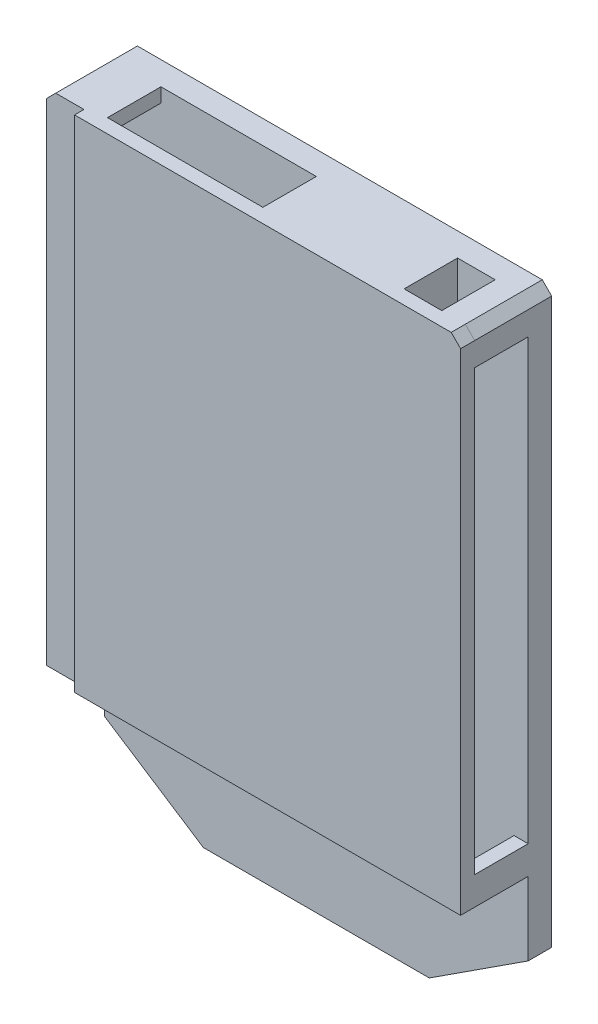
SolidWorks part; units mm, degrees
ref_plane "Front Plane" through (0, 0, 0) normal (0, 0, 1) x (1, 0, 0)
ref_plane "Top Plane" through (0, 0, 0) normal (0, 1, 0) x (1, 0, 0)
ref_plane "Right Plane" through (0, 0, 0) normal (1, 0, 0) x (0, 0, -1)
sketch "Sketch2" plane through (0, 0, 0) normal (0, 0, 1) x (1, 0, 0)
  line L0 (-45, 122) -> (-45, 0.1976)
  line L1 (-24, -13.44) -> (24, -13.44)
  line L2 (45, 0.1976) -> (45, 122)
  line L3 (45, 122) -> (-45, 122)
  line L4 (-45, 0.1976) -> (-24, -13.44)
  line L5 (24, -13.44) -> (45, 0.1976)
  line L6 (49.2788, -47.9725) -> (58.518, -41.9725) construction
  line L7 (-61.482, -41.9725) -> (-52.2428, -47.9725) construction
  point P15 (-45, 6.7015)
  point P16 (0, 0)
  point P17 (-45, 0)
  dimension "D1" = 48
  dimension "D2" = 135.44
extrude "Boss-Extrude1" add sketch "Sketch2" along normal blind 5
chamfer "Chamfer1" distance 2 2 edges at (-45, 122, 2.5) (45, 122, 2.5)
sketch "Sketch4" plane through (0, 0, 5) normal (0, 0, 1) x (1, 0, 0)
  line L0 (-45, 120) -> (-43, 122)
  line L1 (-43, 122) -> (-33, 122)
  line L2 (43, 122) -> (-43, 122) construction
  line L3 (-33, 122) -> (-33, 119)
  line L4 (-33, 119) -> (-41.7574, 119)
  line L5 (-41.7574, 119) -> (-42, 118.7574)
  line L9 (-45, 118.7574) -> (-45, 120)
  line L10 (-42, 118.7574) -> (-45, 118.7574)
  line L11 (-45, 15.7574) -> (-33, 15.7574)
  line L12 (-45, 120) -> (-45, 0.1976) construction
  line L13 (-33, 15.7574) -> (-33, 18.7574)
  line L14 (-33, 18.7574) -> (-45, 18.7574)
  line L15 (-45, 18.7574) -> (-45, 15.7574)
  line L16 (0, 122) -> (30, 122)
  line L17 (30, 122) -> (30, 108)
  line L18 (30, 108) -> (27, 108)
  line L19 (27, 108) -> (27, 119)
  line L20 (27, 119) -> (0, 119)
  line L21 (0, 119) -> (0, 122)
  line L22 (0, 15.7574) -> (30, 15.7574)
  line L23 (30, 15.7574) -> (30, 29.7574)
  line L24 (30, 29.7574) -> (27, 29.7574)
  line L25 (27, 29.7574) -> (27, 18.7574)
  line L26 (27, 18.7574) -> (0, 18.7574)
  line L27 (0, 18.7574) -> (0, 15.7574)
  point P25 (-45, 116.6472)
  point P30 (-39.5053, 120.0532)
  point P31 (-40.4031, 120.3543)
  point P32 (-8.4136, 119)
  point P33 (0, 0)
  dimension "D1" = 100
  dimension "D2" = 3
  dimension "D3" = 3
  dimension "D4" = 3
  dimension "D5" = 3
  dimension "D6" = 3
  dimension "D7" = 3
  dimension "D8" = 72
  dimension "D9" = 14
  dimension "D10" = 30
  dimension "D11" = 12
extrude "Boss-Extrude2" add sketch "Sketch4" along normal blind 11.35
sketch "Sketch5" plane through (0, 0, 16.35) normal (0, 0, 1) x (1, 0, 0)
  line L0 (-33, 122) -> (-43, 122) construction
  line L1 (45, 15.7574) -> (-45, 15.7574)
  line L2 (45, 15.7574) -> (45, 122)
  line L3 (45, 122) -> (-43, 122)
  line L4 (-45, 15.7574) -> (-45, 120)
  line L6 (-45, 118.7574) -> (-45, 18.7574) construction
  line L7 (-43, 122) -> (-45, 120)
  line L8 (45, 0.1976) -> (45, 120) construction
  line L9 (0, 15.7574) -> (30, 15.7574) construction
  point P1 (-45, 122)
  point P5 (-45, 121.6638)
  point P8 (-42.4161, 122)
  point P9 (-38.4712, 122)
  point P14 (45, 17.3911)
extrude "Boss-Extrude3" add sketch "Sketch5" along normal blind 3 contours L2 L1 L4 L7 L3
sketch "Sketch6" plane through (0, 0, 5) normal (0, 0, 1) x (1, 0, 0)
  line L0 (38, 122) -> (43, 122)
  line L1 (43, 122) -> (30, 122) construction
  line L2 (43, 122) -> (45, 120)
  line L3 (45, 120) -> (45, 115)
  line L4 (45, 0.1976) -> (45, 120) construction
  line L5 (45, 115) -> (42, 115)
  line L6 (42, 115) -> (42, 118.7574)
  line L7 (42, 118.7574) -> (41.7574, 119)
  line L8 (41.7574, 119) -> (38, 119)
  line L9 (38, 119) -> (38, 122)
  line L10 (45, 15.7574) -> (39, 15.7574)
  line L11 (39, 15.7574) -> (39, 18.7574)
  line L12 (39, 18.7574) -> (42, 18.7574)
  line L13 (42, 18.7574) -> (42, 21.7574)
  line L14 (42, 21.7574) -> (45, 21.7574)
  line L15 (45, 21.7574) -> (45, 15.7574)
  line L16 (45, 15.7574) -> (-45, 15.7574) construction
  dimension "D1" = 3
  dimension "D2" = 3
  dimension "D3" = 3
  dimension "D4" = 5
  dimension "D5" = 5
  dimension "D6" = 3
  dimension "D7" = 3
  dimension "D8" = 6
  dimension "D9" = 6
extrude "Boss-Extrude4" add sketch "Sketch6" along normal up to surface (11.35 mm away) up to face at (0.5565, 73.4131, 16.35)
chamfer "Chamfer2" distance 2 1 edges at (45, 122, 17.85)
sketch "Sketch8" plane through (0, 0, 19.35) normal (0, 0, 1) x (1, 0, 0)
  line L0 (-37, 15.7574) -> (-37, 122)
  line L1 (45, 15.7574) -> (-45, 15.7574) construction
  line L2 (43, 122) -> (-43, 122) construction
  line L3 (-37, 122) -> (-43, 122)
  line L4 (-43, 122) -> (-45, 120)
  line L5 (-45, 120) -> (-45, 15.7574)
  line L6 (-45, 15.7574) -> (-37, 15.7574)
  line M8 (43, 122) -> (-43, 122)
  line M9 (-43, 122) -> (-45, 120)
  line M10 (-45, 120) -> (-45, 15.7574)
  line M11 (-45, 15.7574) -> (45, 15.7574)
  dimension "D1" = 8
extrude "Cut-Extrude2" cut sketch "Sketch8" against normal blind 2 contours L0 M11 M8 M9 M10 region at (-40.9921, 68.755, 19.35)
